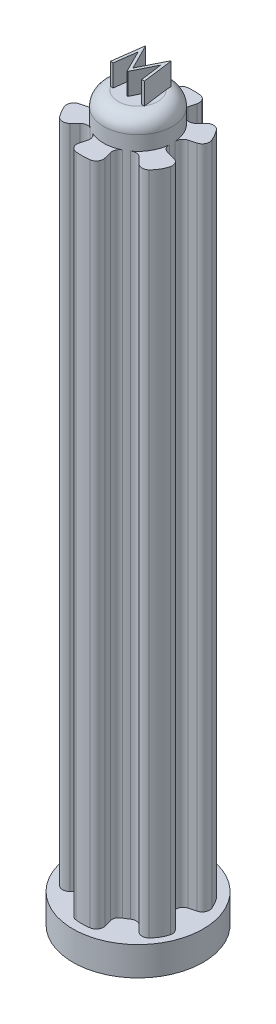
SolidWorks part; units mm, degrees
ref_plane "Front Plane" through (0, 0, 0) normal (0, 0, 1) x (1, 0, 0)
ref_plane "Top Plane" through (0, 0, 0) normal (0, 1, 0) x (1, 0, 0)
ref_plane "Right Plane" through (0, 0, 0) normal (1, 0, 0) x (0, 0, -1)
sketch "Sketch2" plane through (0, 0, 0) normal (0, 1, 0) x (1, 0, 0)
  line L0 (0, 0) -> (0.0739, 0)
  line L2 (2.3008, -0.5891) -> (3.7752, -0.9786)
  line L3 (0.0739, 0) -> (0.1042, -0.0303)
  line L4 (0, 0) -> (0.0858, -0.0446)
  line L5 (1.6802, 1.6786) -> (2.7413, 2.7388)
  line L6 (-1.6794, 1.6794) -> (-2.74, 2.74)
  line L8 (0.6147, 2.2941) -> (1.0029, 3.743)
  line L9 (-0.6147, 2.2941) -> (-1.0029, 3.743)
  line L10 (2.2941, 0.6147) -> (3.743, 1.0029)
  line L11 (0, 0) -> (0.1042, -0.0303)
  line L12 (-2.2941, 0.6147) -> (-3.743, 1.0029)
  line L13 (0.0739, 0) -> (0.0858, -0.0446)
  line L14 (-0.6147, -2.2941) -> (-1.0029, -3.743)
  line L15 (-2.2941, -0.6147) -> (-3.743, -1.0029)
  line L16 (-1.6794, -1.6794) -> (-2.74, -2.74)
  line L17 (0.6814, -2.2752) -> (1.0684, -3.7248)
  line L18 (1.7145, -1.6435) -> (2.7672, -2.6981)
  arc A0 (-2.2941, 0.6147) -> (-2.2941, -0.6147) centre (0, 0) ccw
  arc A1 (-2.74, 2.74) -> (-3.743, 1.0029) centre (0, 0) ccw
  arc A2 (1.0029, 3.743) -> (-1.0029, 3.743) centre (0, 0) ccw
  arc A3 (3.743, 1.0029) -> (2.7413, 2.7388) centre (0, 0) ccw
  arc A5 (-1.0029, -3.743) -> (1.0684, -3.7248) centre (0, 0) ccw
  arc A6 (-3.743, -1.0029) -> (-2.74, -2.74) centre (0, 0) ccw
  arc A7 (-2.74, 2.74) -> (-3.743, 1.0029) centre (0, 0) ccw
  arc A8 (1.0029, 3.743) -> (-1.0029, 3.743) centre (0, 0) ccw
  arc A9 (3.743, 1.0029) -> (2.7413, 2.7388) centre (0, 0) ccw
  arc A10 (-3.743, -1.0029) -> (-2.74, -2.74) centre (0, 0) ccw
  arc A11 (-1.0029, -3.743) -> (1.0684, -3.7248) centre (0, 0) ccw
  arc A12 (2.7672, -2.6981) -> (3.7752, -0.9786) centre (1.7753, -0.9614) ccw
  arc A13 (-0.6147, 2.2941) -> (-1.6794, 1.6794) centre (0, 0) ccw
  arc A14 (1.6802, 1.6786) -> (0.6147, 2.2941) centre (0, 0) ccw
  arc A15 (2.3008, -0.5891) -> (2.2941, 0.6147) centre (0, 0) ccw
  arc A16 (0.6814, -2.2752) -> (1.7145, -1.6435) centre (0, 0) ccw
  arc A17 (-1.6794, -1.6794) -> (-0.6147, -2.2941) centre (0, 0) ccw
  dimension "D1" = 3.875
  dimension "D2" = 2.375
extrude "Boss-Extrude1" add sketch "Sketch2" along normal blind 46 contours L16 A17 L14 A5 L17 A16 L18 A12 L2 A15 L10 A3 L5 A14 L8 A2 L9 A13 L6 A1 L12 A0 L15 A6 L11 L13 L4 L0 L3 region at (0.0225, 0, 0.0171)
sketch "Sketch3" plane through (0, 0, 0) normal (0, -1, 0) x (1, 0, 0)
  circle A0 centre (0, 0) radius 4.5
  dimension "D1" = 9
extrude "Boss-Extrude2" add sketch "Sketch3" along normal blind 2
sketch "Sketch4" plane through (0, 46, 0) normal (0, 1, 0) x (1, 0, 0)
  circle A0 centre (0, 0) radius 2.375
  dimension "D1" = 4.75
extrude "Boss-Extrude3" add sketch "Sketch4" along normal blind 2
fillet "Fillet1" radius 0.5 24 edges at (-2.74, 23, -2.74) (-1.6794, 23, -1.6794) (-0.6147, 23, -2.2941) (-1.0029, 23, -3.743) (1.0029, 23, -3.743) (0.6147, 23, -2.2941) (1.6802, 23, -1.6786) (2.7413, 23, -2.7388) (3.743, 23, -1.0029) (2.2941, 23, -0.6147) (2.3008, 23, 0.5891) (3.7752, 23, 0.9786) (2.7672, 23, 2.6981) (1.7145, 23, 1.6435) (0.6814, 23, 2.2752) (-1.6794, 23, 1.6794) (-2.2941, 23, 0.6147) (-2.2941, 23, -0.6147) (-0.6147, 23, 2.2941) (-3.743, 23, -1.0029) (-3.743, 23, 1.0029) (-2.74, 23, 2.74) (-1.0029, 23, 3.743) (1.0684, 23, 3.7248)
sketch "Sketch5" plane through (0, 48, 0) normal (0, 1, 0) x (1, 0, 0)
  text T0 "M" font "Century Gothic" height in points 8
sketch "Sketch6" plane through (0, -2, 0) normal (0, -1, 0) x (1, 0, 0)
  circle A0 centre (0, 0) radius 1
  dimension "D1" = 2
extrude "Cut-Extrude4" cut sketch "Sketch6" against normal blind 0.5 draft 50
extrude "Boss-Extrude4" add sketch "Sketch5" along normal blind 1.5
fillet "Fillet2" radius 1 1 edges at (0, 48, 2.375)
